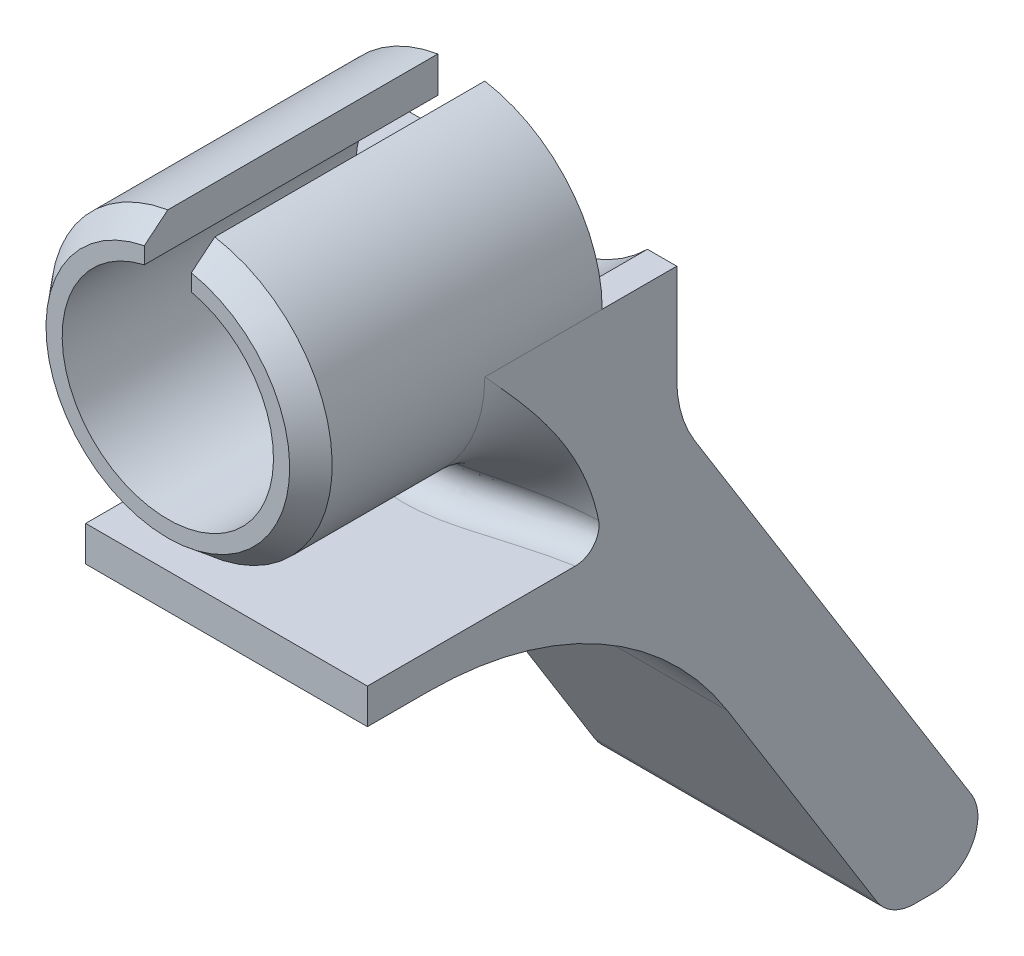
SolidWorks part; units mm, degrees
material "ABS PC"
ref_plane "Front Plane" through (0, 0, 0) normal (0, 0, 1) x (1, 0, 0)
ref_plane "Top Plane" through (0, 0, 0) normal (0, 1, 0) x (1, 0, 0)
ref_plane "Right Plane" through (0, 0, 0) normal (1, 0, 0) x (0, 0, -1)
sketch "Sketch1" plane through (0, 0, 0) normal (0, 0, 1) x (1, 0, 0)
  circle A0 centre (0, 0) radius 12
  dimension "D1" = 24
extrude "Boss-Extrude1" add sketch "Sketch1" along normal blind 25
sketch "Sketch2" plane through (0, 0, 25) normal (0, 0, 1) x (1, 0, 0)
  line L3 (-2, 12) -> (2, 12)
  line L7 (-2, 8.775) -> (-2, 12)
  line L10 (2, 8.775) -> (2, 12)
  arc A0 (-2, 8.775) -> (2, 8.775) centre (0, 0) ccw
  point P1 (0, 12)
  dimension "D1" = 18
  dimension "D4" = 4
  dimension "D6" = 12
extrude "Cut-Extrude1" cut sketch "Sketch2" against normal up to surface (25 mm away) up to face at (12, 0, 0)
sketch "Sketch3" plane through (0, 0, 0) normal (0, 0, -1) x (-1, 0, 0)
  line L0 (-9.5028, 0) -> (-12, 0)
  line L1 (9.5028, 0) -> (12, 0)
  line L2 (12, 0) -> (12, -17.8)
  line L3 (-12, 0) -> (-12, -17.8)
  line L4 (12, -17.8) -> (-12, -17.8)
  arc A0 (-9.5028, 0) -> (9.5028, 0) centre (0, 9.5) ccw
  circle A1 centre (0, 0) radius 12 construction
  point P11 (0, -3.937)
  dimension "D1" = 17.8
  dimension "D2" = 13.437
  dimension "D3" = 3.937
extrude "Boss-Extrude2" add sketch "Sketch3" along normal blind 6.35
fillet "Fillet1" radius 7.62 1 edges at (0, -9, 0)
fillet "Fillet2" [suppressed] radius 7.62
sketch "Sketch4" plane through (12, 0, 0) normal (1, 0, 0) x (0, 0, -1)
  line L0 (0, -17.8) -> (24.4958, -57.17)
  line L1 (6.35, -17.8) -> (0, -17.8) construction
  line L2 (32.0109, -52.4204) -> (6.35, -11.1778)
  line L3 (6.35, 0) -> (6.35, -17.8) construction
  line L4 (0, -17.8) -> (6.35, -11.1778)
  line L5 (24.4958, -57.17) -> (32.0109, -57.17)
  line L6 (32.0109, -57.17) -> (32.0109, -52.4204)
  dimension "D1" = 39.37
  dimension "D2" = 8.89
  dimension "D3" = 9.1748
  dimension "D4" = 4.7496
extrude "Boss-Extrude3" add sketch "Sketch4" against normal up to surface (24 mm away) up to face at (-12, -8.9, -3.175)
fillet "Fillet6" radius 3.81 3 edges at (0, -57.17, -24.4958) (0, -57.17, -32.0109) (0, -52.4204, -32.0109)
ref_plane "Plane1" through (0, -17.8, 0) normal (0, 1, 0) x (1, 0, 0)
sketch "Sketch5" plane through (0, -17.8, 0) normal (0, 1, 0) x (1, 0, 0)
  line L0 (-12, 23.3775) -> (-12, 0) construction
  line L1 (-12, 6) -> (12, 6)
  line L2 (-12, 6) -> (-12, -20)
  line L3 (-12, -20) -> (12, -20)
  line L4 (12, 6) -> (12, -20)
  line L5 (12, -25) -> (12, 0) construction
  line L6 (-12, 0) -> (12, 0) construction
  dimension "D1" = 20
  dimension "D2" = 6
extrude "Boss-Extrude4" add sketch "Sketch5" against normal blind 3
fillet "Fillet7" radius 30 1 edges at (0, -20.8, -1.8666)
chamfer "Chamfer1" distance 2 angle 39 1 edges at (0, -12, 25) first distance on face at (0, 2.526, 8.3333)
fillet "Fillet8" radius 10 1 edges at (0, -12, 0)
fillet "Fillet9" radius 2 1 edges at (0, -17.8, 0.9248)
fillet "Fillet10" radius 10 1 edges at (0, -11.1778, -6.35)
